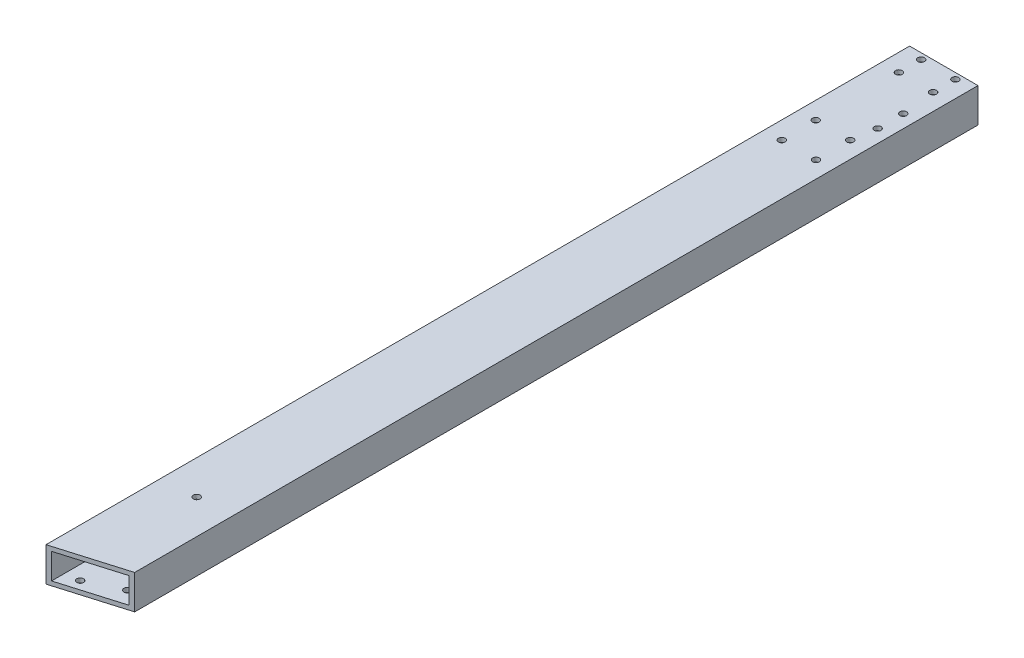
SolidWorks part; units mm, degrees
material "1060 Alloy"
ref_plane "Front Plane" through (0, 0, 0) normal (0, 0, 1) x (1, 0, 0)
ref_plane "Top Plane" through (0, 0, 0) normal (0, 1, 0) x (1, 0, 0)
ref_plane "Right Plane" through (0, 0, 0) normal (1, 0, 0) x (0, 0, -1)
sketch "Sketch1" plane through (0, 0, 0) normal (0, 0, 1) x (1, 0, 0)
  line L0 (-22.225, 9.525) -> (22.225, 9.525)
  line L2 (-25.4, 12.7) -> (25.4, 12.7)
  line L3 (-25.4, 12.7) -> (-25.4, -12.7)
  line L4 (-25.4, -12.7) -> (25.4, -12.7)
  line L5 (25.4, 12.7) -> (25.4, -12.7)
  line L10 (22.225, 9.525) -> (22.225, -9.525)
  line L11 (-22.225, -9.525) -> (22.225, -9.525)
  line L12 (-22.225, 9.525) -> (-22.225, -9.525)
  point P12 (0, 12.7)
  point P14 (25.4, 0)
  dimension "Wall Thickness" = 3.175
  dimension "Outside Width" = 50.8
  dimension "Outside Height" = 25.4
  dimension "Inside Height" = 19.05
  dimension "Inside Width" = 44.45
sketch "Sketch2" plane through (0, 0, 0) normal (1, 0, 0) x (0, 0, -1)
  line L0 (320.675, 0) -> (-320.675, 0)
  point P4 (0, 0)
  point P7 (-320.675, 0)
  point P10 (320.675, 0)
  dimension "Length" = 641.35
sketch "Sketch3" plane through (0, 0, 0) normal (0, 0, 1) x (1, 0, 0)
  line L21 (25.4, 12.7) -> (-25.4, 12.7)
  line L22 (25.4, -12.7) -> (25.4, 12.7)
  line L23 (-25.4, -12.7) -> (25.4, -12.7)
  line L24 (-25.4, 12.7) -> (-25.4, -12.7)
  line L25 (25.4, 12.7) -> (-25.4, 12.7)
  line L26 (25.4, -12.7) -> (25.4, 12.7)
  line L27 (-25.4, -12.7) -> (25.4, -12.7)
  line L28 (-25.4, 12.7) -> (-25.4, -12.7)
  line L29 (22.225, 9.525) -> (-22.225, 9.525)
  line L30 (22.225, -9.525) -> (22.225, 9.525)
  line L31 (-22.225, -9.525) -> (22.225, -9.525)
  line L32 (-22.225, 9.525) -> (-22.225, -9.525)
  line L33 (22.225, 9.525) -> (-22.225, 9.525)
  line L34 (22.225, -9.525) -> (22.225, 9.525)
  line L35 (-22.225, -9.525) -> (22.225, -9.525)
  line L36 (-22.225, 9.525) -> (-22.225, -9.525)
  dimension "D1" = 0
  dimension "D2" = 0
extrude "Boss-Extrude1" add sketch "Sketch3" along normal up to vertex (320.675 mm away) and the other way up to vertex (320.675 mm away) up to point (0, 0, 320.675) other way up to point (0, 0, -320.675)
sketch "Drawing Reference" plane through (0, 0, 0) normal (1, 0, 0) x (0, 0, -1)
  line L0 (-320.675, 0) -> (320.675, 0) construction
  line L1 (0, -12.7) -> (0, 12.7) construction
  line L2 (-320.675, -12.7) -> (320.675, -12.7) construction
  line L5 (-320.675, 12.7) -> (320.675, 12.7) construction
  point P7 (-284.099, 0)
  point P8 (284.099, 0)
  dimension "D1" = 36.576
sketch "Sketch4" plane through (0, 12.7, 0) normal (0, 1, 0) x (1, 0, 0)
  line L0 (-25.4, -320.675) -> (25.4, -305.6274)
  line L1 (25.4, -320.675) -> (25.4, 320.675) construction
  line L2 (25.4, -320.675) -> (-25.4, -320.675)
  dimension "D1" = 16.5
extrude "Cut-Extrude1" cut sketch "Sketch4" against normal through all and the other way through all flip side to cut
sketch "Sketch6" plane through (0, -12.7, 0) normal (0, -1, 0) x (1, 0, 0)
  line L0 (25.4, 305.6274) -> (22.1108, 294.5233) construction
  line L1 (25.4, 279.2824) -> (22.225, 279.2824) construction
  line L2 (25.4, 305.6274) -> (25.4, -320.675) construction
  line L3 (22.225, 279.2824) -> (22.225, 313.1512) construction
  line L4 (22.1108, 294.5233) -> (11.811, 297.5742) construction
  line L5 (-11.811, 250.3501) -> (-11.811, 328.3651) construction
  line L6 (-25.4, 320.675) -> (-27.5213, 313.5136) construction
  line L7 (-25.4, 287.6223) -> (-22.225, 287.6223) construction
  line L8 (-25.4, 320.675) -> (-25.4, -320.675) construction
  line L9 (-22.225, 287.6223) -> (-22.225, 328.3651) construction
  line L10 (-27.5213, 313.5136) -> (-11.811, 308.86) construction
  line L11 (11.811, 250.3501) -> (11.811, 313.1512) construction
  line L12 (-27.5213, 313.5136) -> (-36.5388, 283.071) construction
  line L13 (22.1108, 294.5233) -> (13.0933, 264.0807) construction
  line L14 (-37.6746, 250.3501) -> (48.6057, 250.3501) construction
  line L15 (-11.811, 287.6223) -> (-11.811, 328.3651) construction
  line L16 (11.811, 279.2824) -> (11.811, 313.1512) construction
  line L17 (-36.5388, 283.071) -> (-11.811, 275.7463) construction
  line L18 (13.0933, 264.0807) -> (11.811, 264.4606) construction
  dimension "D1" = 10.414
  dimension "D2" = 10.414
hole_wizard "#10 Clearance Hole1" positions "Sketch7" profile "Sketch8" hole size "#10" standard "ANSI Inch"
sketch "Sketch7" plane through (0, -12.7, 0) normal (0, -1, 0) x (-1, 0, 0)
  point P0 (-11.811, -264.4606)
  point P3 (11.811, -275.7463)
  point P7 (-11.811, -297.5742)
  point P10 (11.811, -308.86)
sketch "Sketch8" plane through (11.811, -12.7, 264.4606) normal (1, 0, 0) x (0, 0, -1)
  line L0 (0, 0) -> (0, 6.5757)
  line L1 (0, 6.5757) -> (2.4892, 5.08)
  line L2 (2.4892, 5.08) -> (2.4892, 0)
  line L5 (2.4892, 0) -> (0, 0)
  line L10 (0, 6.5757) -> (-2.4892, 5.08) construction
  line L11 (0, -6.35) -> (0, 107.95) construction
  dimension "Hole Dia." = 4.9784
  dimension "Hole Depth" = 5.08
  dimension "Drill Angle" = 118
sketch "Sketch9" plane through (0, 12.7, 0) normal (0, 1, 0) x (1, 0, 0)
  line L0 (-12.3709, 316.23) -> (-9.8309, 316.23) construction
  line L2 (-9.1044, 314.5662) -> (-9.0928, 314.5269) construction
  line L3 (10.4891, 316.23) -> (13.0291, 316.23) construction
  line L4 (13.0291, 299.72) -> (10.4891, 299.72) construction
  line L5 (-9.8309, 299.72) -> (-12.3709, 299.72) construction
hole_wizard "#10 Clearance Hole2" positions "Sketch10" profile "Sketch11" hole size "#10" standard "ANSI Inch"
sketch "Sketch10" plane through (0, 12.7, 0) normal (0, 1, 0) x (1, 0, 0)
  point P0 (13.0291, 299.72)
  point P3 (-12.3709, 299.72)
  point P6 (13.0291, 316.23)
  point P9 (-12.3709, 316.23)
sketch "Sketch11" plane through (13.0291, 12.7, -299.72) normal (1, 0, 0) x (0, 0, 1)
  line L0 (0, 0) -> (0, 6.5757)
  line L1 (0, 6.5757) -> (2.4892, 5.08)
  line L2 (2.4892, 5.08) -> (2.4892, 0)
  line L5 (2.4892, 0) -> (0, 0)
  line L10 (0, 6.5757) -> (-2.4892, 5.08) construction
  line L11 (0, -6.35) -> (0, 107.95) construction
  dimension "Hole Dia." = 4.9784
  dimension "Hole Depth" = 5.08
  dimension "Drill Angle" = 118
sketch "Sketch12" plane through (0, 12.7, 0) normal (0, 1, 0) x (1, 0, 0)
  line L0 (-12.3709, 238.125) -> (13.0291, 238.125) construction
  line L1 (13.0291, 238.125) -> (13.0291, 212.725) construction
  line L2 (13.0291, 212.725) -> (-12.3709, 212.725) construction
  line L3 (-12.3709, 212.725) -> (-12.3709, 238.1868) construction
hole_wizard "#10 Clearance Hole3" positions "Sketch13" profile "Sketch14" hole size "#10" standard "ANSI Inch" end condition through all
sketch "Sketch13" plane through (0, 12.7, 0) normal (0, 1, 0) x (1, 0, 0)
  point P0 (-12.3709, 212.725)
  point P3 (13.0291, 212.725)
  point P6 (13.0291, 238.125)
  point P9 (-12.5651, 238.125)
  point P12 (15.7366, 274.8363)
  point P15 (15.7366, 255.7863)
sketch "Sketch14" plane through (-12.3709, 12.7, -212.725) normal (1, 0, 0) x (0, 0, 1)
  line L0 (0, 0) -> (0, 25.4)
  line L1 (0, 25.4) -> (2.4892, 25.4)
  line L2 (2.4892, 25.4) -> (2.4892, 0)
  line L5 (2.4892, 0) -> (0, 0)
  line L11 (0, -6.35) -> (0, 107.95) construction
  dimension "Thru Hole Dia." = 4.9784
  dimension "Thru Hole Depth" = 25.4
sketch "Sketch17" plane through (0, 12.7, 0) normal (0, 1, 0) x (1, 0, 0)
  point P0 (-0.0762, -234.0972)
hole_wizard "#10 Clearance Hole4" positions "Sketch15" profile "Sketch16" hole size "#10" standard "ANSI Inch" end condition through all
sketch "Sketch15" plane through (0, 12.7, 0) normal (0, 1, 0) x (1, 0, 0)
  point P0 (-0.0762, -234.0972)
  point P2 (-0.0762, -234.0972)
sketch "Sketch16" plane through (-0.0762, 12.7, 234.0972) normal (1, 0, 0) x (0, 0, 1)
  line L0 (0, 0) -> (0, 25.4)
  line L1 (0, 25.4) -> (2.4892, 25.4)
  line L2 (2.4892, 25.4) -> (2.4892, 0)
  line L5 (2.4892, 0) -> (0, 0)
  line L11 (0, -6.35) -> (0, 107.95) construction
  dimension "Thru Hole Dia." = 4.9784
  dimension "Thru Hole Depth" = 25.4
equation "\"D1@Drawing Reference\"=\"Outside Width@Sketch1\" * 0.72"
